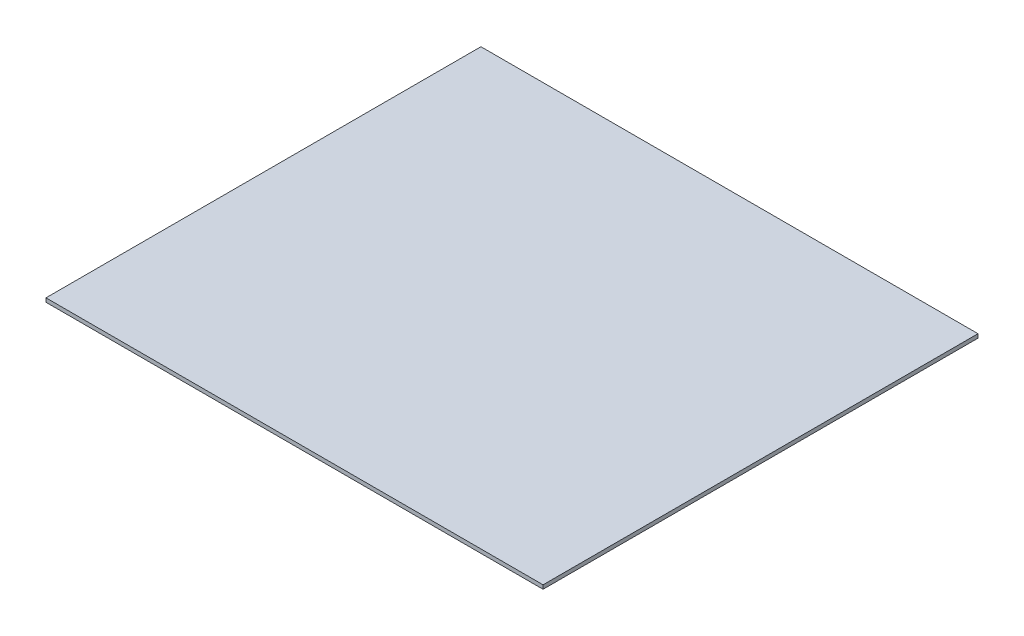
SolidWorks part; units mm, degrees
ref_plane "Front Plane" through (0, 0, 0) normal (0, 0, 1) x (1, 0, 0)
ref_plane "Top Plane" through (0, 0, 0) normal (0, 1, 0) x (1, 0, 0)
ref_plane "Right Plane" through (0, 0, 0) normal (1, 0, 0) x (0, 0, -1)
sketch "Sketch1" plane through (0, 0, 0) normal (0, 1, 0) x (1, 0, 0)
  line L1 (-101.6, 88.9) -> (101.6, 88.9)
  line L2 (-101.6, 88.9) -> (-101.6, -88.9)
  line L3 (-101.6, -88.9) -> (101.6, -88.9)
  line L4 (101.6, 88.9) -> (101.6, -88.9)
  dimension "D1" = 203.2
  dimension "D2" = 177.8
  dimension "D3" = 101.6
  dimension "D4" = 88.9
base flange "Base-Flange1" sketch "Sketch1" thickness 1.5875 reverse thickness direction no parameters "D1"=0.7366
sketch "Bend-Lines1" plane through (0, 0, 0) normal (0, 1, 0) x (1, 0, 0)
sketch "Bounding-Box1" plane through (0, 0, 0) normal (0, 1, 0) x (1, 0, 0)
sheet metal parameters "Sheet-Metal1" thickness 1.5875 parameters "D1"=0.7366
flat pattern "Flat-Pattern1" [suppressed]
sketch "Bend-Lines2" plane through (0, 0, 0) normal (0, 1, 0) x (1, 0, 0)
sketch "Bounding-Box2" [suppressed] plane through (0, 0, 0) normal (0, 1, 0) x (1, 0, 0)
